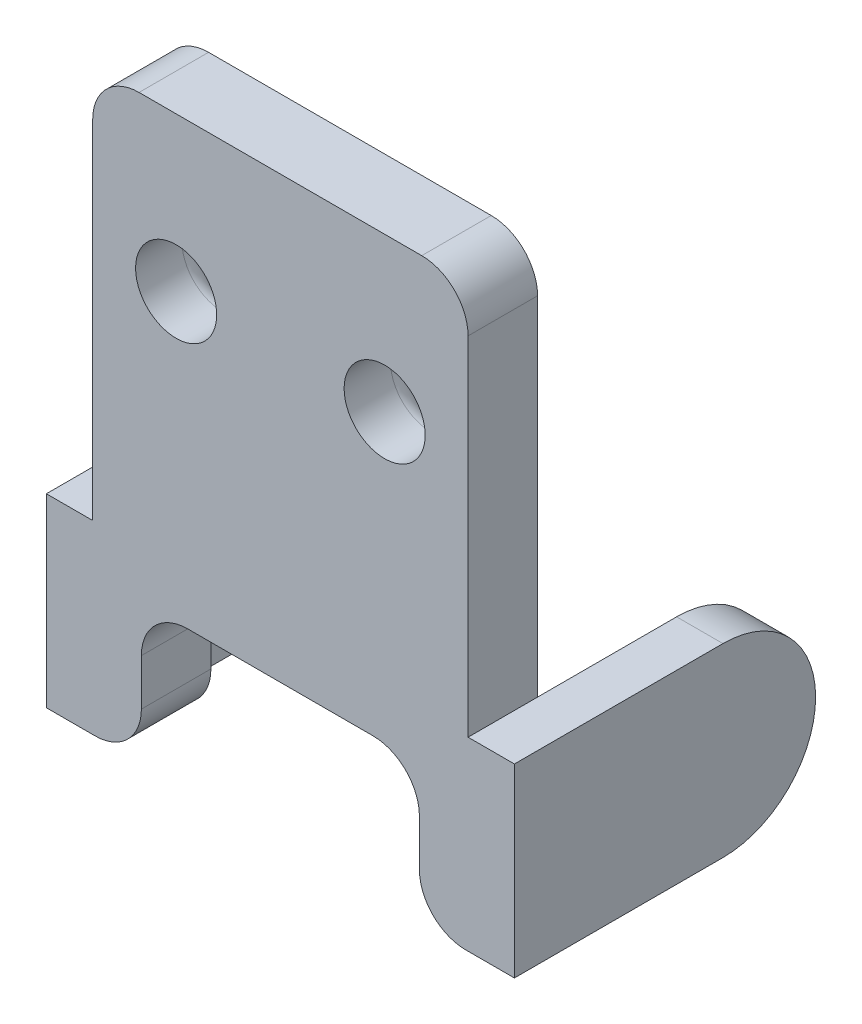
SolidWorks part; units mm, degrees
ref_plane "Plan de face" through (0, 0, 0) normal (0, 0, 1) x (1, 0, 0)
ref_plane "Plan de dessus" through (0, 0, 0) normal (0, 1, 0) x (1, 0, 0)
ref_plane "Plan de droite" through (0, 0, 0) normal (1, 0, 0) x (0, 0, -1)
sketch "Esquisse1" plane through (0, 0, 0) normal (0, 0, 1) x (1, 0, 0)
  line L1 (0, 0) -> (16.2, 0)
  line L2 (0, 0) -> (0, 25)
  line L3 (0, 25) -> (16.2, 25)
  line L4 (16.2, 0) -> (16.2, 25)
  dimension "D1" = 16.2
  dimension "D2" = 25
extrude "Boss.-Extru.1" add sketch "Esquisse1" along normal blind 3
sketch "Esquisse2" plane through (0, 0, 0) normal (-1, 0, 0) x (0, 0, 1)
  line L0 (0, 25) -> (0, 0) construction
  line L1 (3, 0) -> (-10, 0)
  line L2 (3, 0) -> (3, 8)
  line L3 (3, 8) -> (-10, 8)
  line L4 (-10, 0) -> (-10, 8)
  dimension "D1" = 8
  dimension "D2" = 10
extrude "Boss.-Extru.2" add sketch "Esquisse2" along normal blind 2
sketch "Esquisse3" plane through (0, 0, 0) normal (1, 0, 0) x (0, 0, -1)
  line L0 (0, 8) -> (0, 0) construction
  circle A0 centre (7, 4.0358) radius 1.8
  dimension "D1" = 3.6
  dimension "D2" = 7
extrude "Boss.-Extru.3" add sketch "Esquisse3" along normal blind 1.5
sketch "Esquisse5" plane through (16.2, 0, 0) normal (1, 0, 0) x (0, 0, -1)
  line L0 (0, 0) -> (0, 25) construction
  line L1 (-3, 0) -> (10, 0)
  line L2 (-3, 0) -> (-3, 8)
  line L3 (-3, 8) -> (10, 8)
  line L4 (10, 0) -> (10, 8)
  dimension "D1" = 10
  dimension "D2" = 8
extrude "Boss.-Extru.4" add sketch "Esquisse5" along normal blind 2
sketch "Esquisse6" plane through (16.2, 0, 0) normal (-1, 0, 0) x (0, 0, 1)
  line L0 (0, 8) -> (0, 25) construction
  circle A0 centre (-7, 3.8797) radius 1.8
  point P4 (0, 16.5)
  dimension "D1" = 3.6
  dimension "D2" = 7
extrude "Boss.-Extru.5" add sketch "Esquisse6" along normal blind 1.5
sketch "Esquisse7" plane through (0, 0, 0) normal (0, 0, -1) x (-1, 0, 0)
  line L0 (0, 0) -> (-16.2, 0) construction
  line L1 (-14.1, 0) -> (-2.1, 0)
  line L2 (-14.1, 0) -> (-14.1, 6)
  line L3 (-14.1, 6) -> (-2.1, 6)
  line L4 (-2.1, 0) -> (-2.1, 6)
  line L5 (-16.2, 25) -> (0, 25) construction
  point P6 (-8.1, 25)
  point P9 (-8.1, 6)
  dimension "D1" = 0
  dimension "D2" = 12
  dimension "D3" = 6
extrude "Enlèv. mat.-Extru.1" cut sketch "Esquisse7" against normal up to next
sketch "Esquisse8" plane through (0, 0, 0) normal (0, 0, -1) x (-1, 0, 0)
  line L0 (-16.2, 25) -> (0, 25) construction
  circle A0 centre (-12.6, 18.3601) radius 1.75
  circle A1 centre (-3.6, 18.3601) radius 1.75
  point P6 (-8.1, 25)
  dimension "D1" = 3.5
  dimension "D2" = 3.5
  dimension "D3" = 4.5
  dimension "D4" = 4.5
extrude "Enlèv. mat.-Extru.2" cut sketch "Esquisse8" against normal up to next
fillet "Congé1" radius 1 2 edges at (1.85, 18.3601, 0) (10.85, 18.3601, 0)
fillet "Congé2" radius 4 4 edges at (-1, 8, -10) (-1, 0, -10) (17.2, 8, -10) (17.2, 0, -10)
fillet "Congé3" radius 2 4 edges at (2.1, 0, 1.5) (2.1, 6, 1.5) (14.1, 6, 1.5) (14.1, 0, 1.5)
fillet "Congé4" radius 2 2 edges at (0, 25, 1.5) (16.2, 25, 1.5)
fillet "Congé5" [suppressed] radius 1
